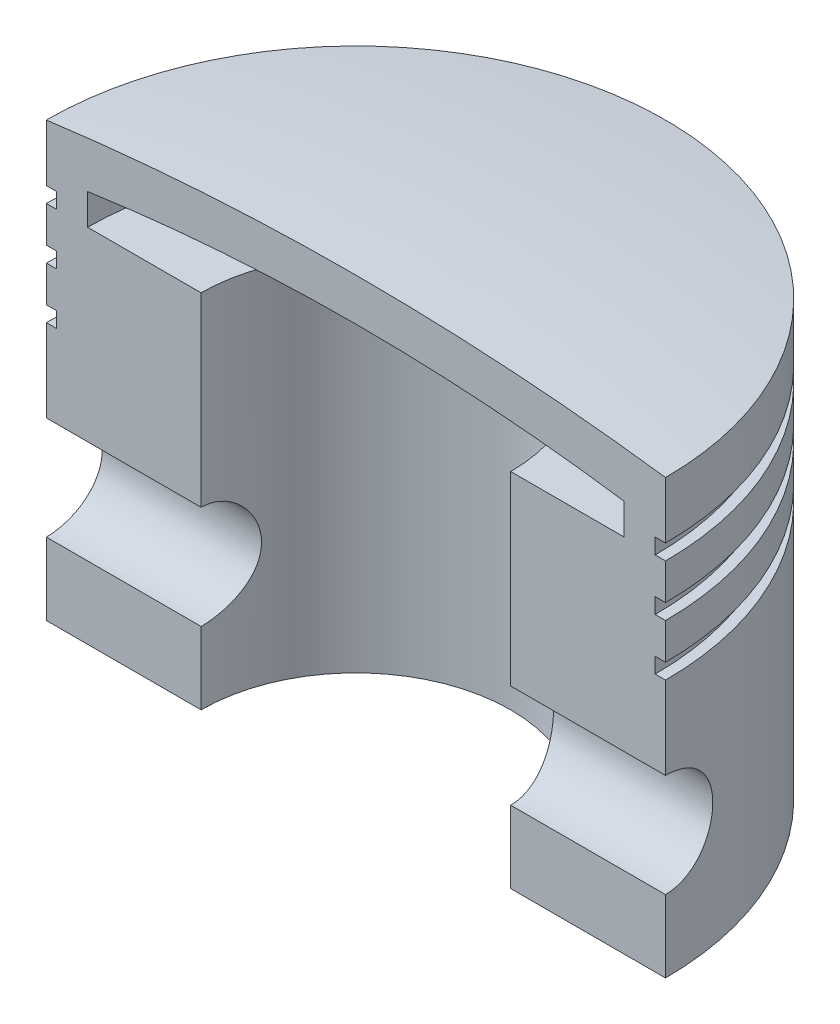
SolidWorks part; units mm, degrees
ref_plane "Front Plane" through (0, 0, 0) normal (0, 0, 1) x (1, 0, 0)
ref_plane "Top Plane" through (0, 0, 0) normal (0, 1, 0) x (1, 0, 0)
ref_plane "Right Plane" through (0, 0, 0) normal (1, 0, 0) x (0, 0, -1)
sketch "Sketch1" plane through (0, 0, 0) normal (0, 0, 1) x (1, 0, 0)
  line L0 (0, 0) -> (0, 45)
  line L1 (-30, 0) -> (30, 0)
  line L2 (30, 0) -> (30, 42)
  line L3 (-26, 35) -> (-26, 38)
  line L4 (15, 0) -> (15, 35)
  line L5 (15, 35) -> (26, 35)
  line L6 (26, 35) -> (26, 38)
  line L7 (26, 38) -> (-26, 38)
  line L8 (-30, 0) -> (-30, 42)
  line L9 (-15, 35) -> (-26, 35)
  line L10 (-15, 0) -> (-15, 35)
  line L11 (0, 45) -> (0, 53.1478) construction
  arc A1 (-26, 38) -> (26, 38) centre (0, -141.5732) cw
  arc A2 (-30, 42) -> (30, 42) centre (0, -183.7098) cw
  point P16 (0, 38)
  dimension "D1" = 45
  dimension "D2" = 15
  dimension "D3" = 3
  dimension "D4" = 35
  dimension "D5" = 42
  dimension "D6" = 26
  dimension "D7" = 30
revolve "Revolve2" add sketch "Sketch1" angle 360 about L11 region at (21.1952, 22.3817, 0)
sketch "Sketch2" plane through (0, 0, 0) normal (1, 0, 0) x (0, 0, -1)
  line L0 (0, 0) -> (0, 49.9723) construction
  circle A0 centre (0, 12) radius 5
  dimension "D1" = 10
  dimension "D2" = 12
extrude "Cut-Extrude1" cut sketch "Sketch2" against normal through all both and the other way through all
ref_axis "Axis1" through (0, 42, 0) along (0, -1, 0)
sketch "Sketch3" plane through (0, 0, 0) normal (1, 0, 0) x (0, 0, -1)
  line L0 (30, 0) -> (30, 25)
  line L1 (30, 0) -> (30, 42) construction
  line L2 (30, 25) -> (29, 25)
  line L3 (29, 25) -> (29, 26.5)
  line L4 (29, 26.5) -> (30, 26.5)
  line L5 (30, 26.5) -> (30, 30)
  line L6 (30, 30) -> (29, 30)
  line L7 (29, 30) -> (29, 31.5)
  line L8 (29, 31.5) -> (30, 31.5)
  line L9 (30, 31.5) -> (30, 35)
  line L10 (30, 35) -> (29, 35)
  line L11 (29, 35) -> (29, 36.5)
  line L12 (29, 36.5) -> (30, 36.5)
  line L13 (30, 36.5) -> (30, 42)
  line L14 (0, 42) -> (30, 42)
  line L15 (0, 42) -> (0, 0) construction
  line L16 (0, 0) -> (30, 0)
  line L17 (30, 36.5) -> (30, 25)
  line L18 (0, 42) -> (0, 0) construction
  dimension "D1" = 25
  dimension "D2" = 1
  dimension "D3" = 1.5
  dimension "D4" = 5
  dimension "D5" = 5
revolve "Cut-Revolve1" cut sketch "Sketch3" angle 360 about L18 region at (0, 35.75, -29.5) region at (0, 30.75, -29.5) region at (0, 25.75, -29.5)
sketch "Sketch4" plane through (0, 0, 0) normal (0, 0, 1) x (1, 0, 0)
  line L1 (-52.4513, 54.2349) -> (51.2655, 54.2349)
  line L2 (-52.4513, 54.2349) -> (-52.4513, -11.0414)
  line L3 (-52.4513, -11.0414) -> (51.2655, -11.0414)
  line L4 (51.2655, 54.2349) -> (51.2655, -11.0414)
extrude "Cut-Extrude2" cut sketch "Sketch4" along normal blind 40
